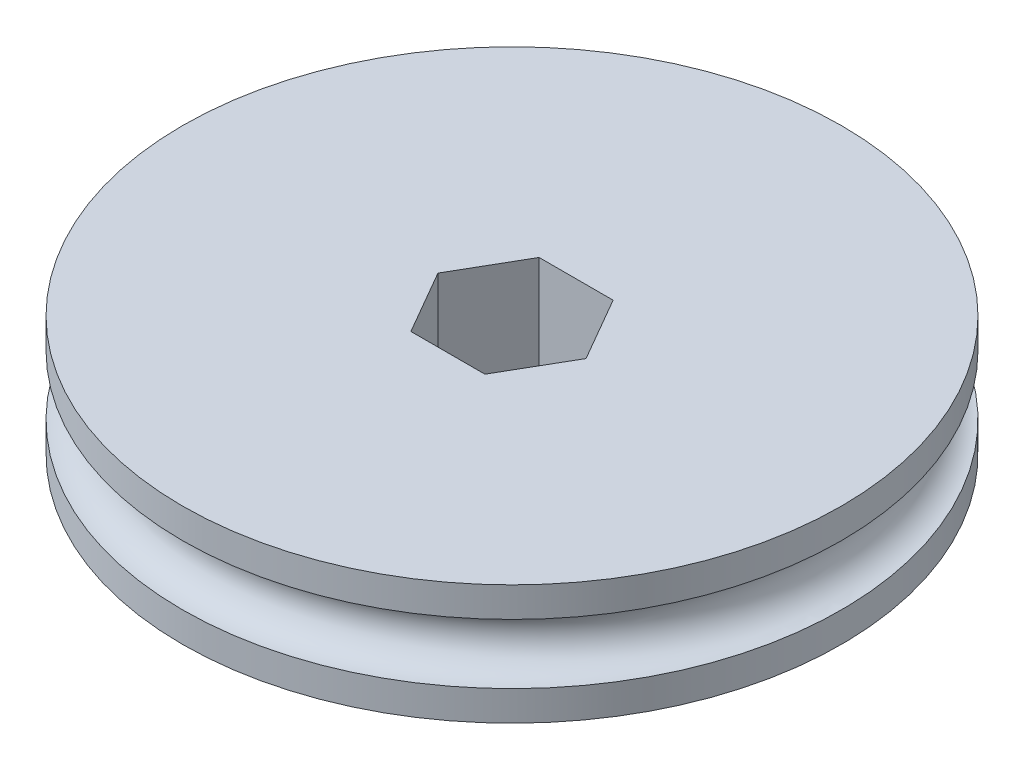
SolidWorks part; units mm, degrees
ref_plane "Front" through (0, 0, 0) normal (0, 0, 1) x (1, 0, 0)
ref_plane "Top" through (0, 0, 0) normal (0, 1, 0) x (1, 0, 0)
ref_plane "Right" through (0, 0, 0) normal (1, 0, 0) x (0, 0, -1)
sketch "Sketch1" plane through (0, 0, 0) normal (0, 1, 0) x (1, 0, 0)
  line L1 (7.8456, 0) -> (3.9228, 6.7945)
  line L2 (3.9228, 6.7945) -> (-3.9228, 6.7945)
  line L3 (-3.9228, 6.7945) -> (-7.8456, 0)
  line L4 (-7.8456, 0) -> (-3.9228, -6.7945)
  line L5 (-3.9228, -6.7945) -> (3.9228, -6.7945)
  line L6 (3.9228, -6.7945) -> (7.8456, 0)
  circle A0 centre (0, 0) radius 6.7945 construction
  circle A1 centre (0, 0) radius 34.925
  dimension "D1" = 69.85
extrude "Boss-Extrude1" add sketch "Sketch1" along normal blind 12.7
ref_plane "Mid_Plane" through (0, 6.35, 0) normal (0, -1, 0) x (-1, 0, 0)
sketch "Sketch4" plane through (-6.35, 6.35, 0) normal (0, 0, -1) x (0, 1, 0)
  line L0 (-6.35, 6.35) -> (-6.35, 41.275) construction
  line L1 (-6.35, 41.275) -> (0, 41.275) construction
  line L3 (6.35, 41.275) -> (-6.35, 41.275) construction
  line L4 (0, 41.275) -> (6.35, 41.275) construction
  line L5 (-6.35, 41.275) -> (-6.35, -28.575) construction
  circle A1 centre (0, 41.275) radius 3.175
  dimension "D3" = 6.35
ref_axis "Axis1" through (0, 12.7, 0) along (0, -1, 0)
revolve "Cut-Revolve1" cut sketch "Sketch4" angle 360 about axis through (0, 12.7, 0) along (0, -1, 0)
